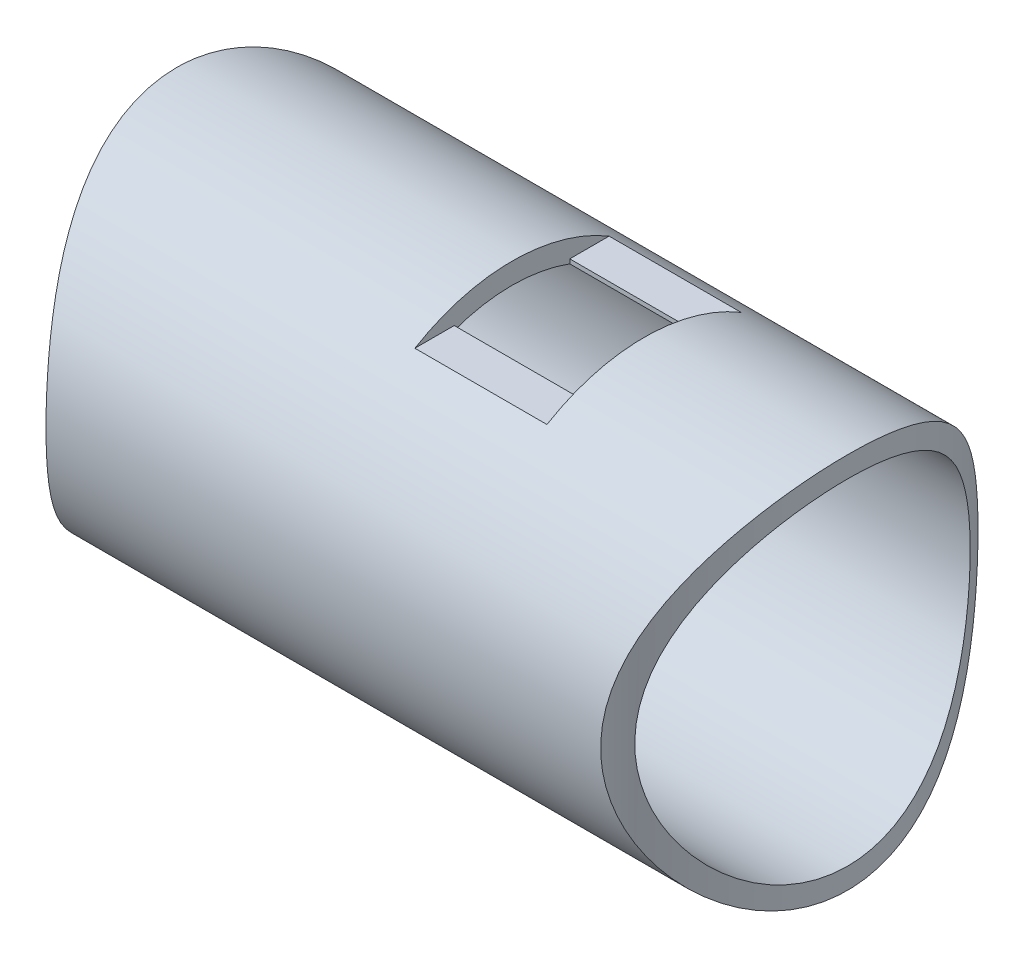
SolidWorks part; units mm, degrees
ref_plane "Front Plane" through (0, 0, 0) normal (0, 0, 1) x (1, 0, 0)
ref_plane "Top Plane" through (0, 0, 0) normal (0, 1, 0) x (1, 0, 0)
ref_plane "Right Plane" through (0, 0, 0) normal (1, 0, 0) x (0, 0, -1)
sketch "Sketch1" plane through (0, 0, 0) normal (1, 0, 0) x (0, 0, -1)
  circle A0 centre (0, 0) radius 57.15
  circle A1 centre (0, 0) radius 50.8
  dimension "D1" = 114.3
  dimension "D2" = 6.35
extrude "Boss-Extrude1" add sketch "Sketch1" along normal blind 101.6 and the other way blind 101.6
sketch "Sketch3" plane through (0, 0, 0) normal (0, 0, 1) x (1, 0, 0)
  line L0 (62.865, 0) -> (-62.865, 0) construction
  line L1 (0, 59) -> (40, 59)
  line L2 (0, 59) -> (0, 49)
  line L3 (0, 49) -> (40, 49)
  line L4 (40, 59) -> (40, 49)
  line L5 (0, -62.865) -> (0, 62.865) construction
  dimension "D1" = 49
  dimension "D2" = 10
  dimension "D3" = 40
  dimension "D4" = 0
extrude "Cut-Extrude3" cut sketch "Sketch3" against normal through all and the other way through all
sketch "Sketch5" plane through (0, 49, 0) normal (0, 1, 0) x (1, 0, 0)
  line L1 (40, -13.403) -> (40, -29.413) construction
  line L2 (40, -17.5) -> (0, -17.5)
  line L3 (40, -17.5) -> (40, 17.5)
  line L4 (40, 17.5) -> (0, 17.5)
  line L5 (0, -17.5) -> (0, 17.5)
  line L6 (0, -62.865) -> (0, 62.865) construction
  line L8 (-62.865, 0) -> (62.865, 0) construction
  point P0 (0, 0)
  dimension "D1" = 35
  dimension "D2" = 17.5
extrude "Cut-Extrude5" cut sketch "Sketch5" against normal blind 18.15
sketch "Sketch6" plane through (0, 0, 0) normal (0, 1, 0) x (1, 0, 0)
  line L1 (126.0829, 122.4438) -> (-126.0829, 122.4438)
  line L2 (126.0829, 122.4438) -> (126.0829, -122.4438)
  line L3 (126.0829, -122.4438) -> (-126.0829, -122.4438)
  line L4 (-126.0829, 122.4438) -> (-126.0829, -122.4438)
  line L5 (126.0829, 122.4438) -> (-126.0829, -122.4438) construction
  line L6 (126.0829, -122.4438) -> (-126.0829, 122.4438) construction
  circle A0 centre (0, 0) radius 101.6
  dimension "D1" = 203.2
extrude "Cut-Extrude6" cut sketch "Sketch6" against normal through all and the other way through all
